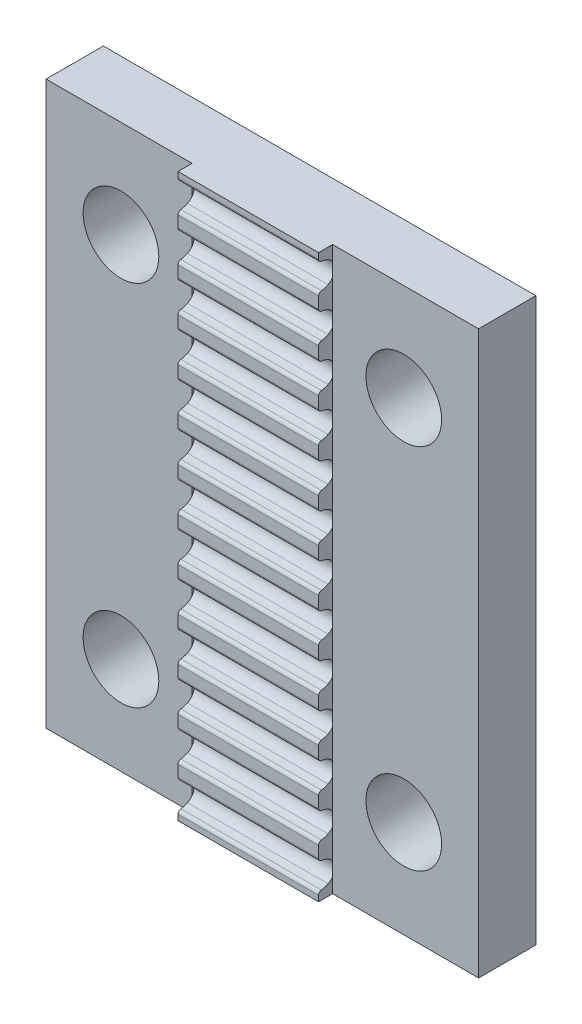
SolidWorks part; units mm, degrees
ref_plane "Piano frontale" through (0, 0, 0) normal (0, 0, 1) x (1, 0, 0)
ref_plane "Piano superiore" through (0, 0, 0) normal (0, 1, 0) x (1, 0, 0)
ref_plane "Piano destro" through (0, 0, 0) normal (1, 0, 0) x (0, 0, -1)
sketch "Schizzo1" plane through (0, 0, 0) normal (0, 0, 1) x (1, 0, 0)
  line L1 (-10, -13) -> (10, -13)
  line L2 (-10, -13) -> (-10, 13)
  line L3 (-10, 13) -> (10, 13)
  line L4 (10, -13) -> (10, 13)
  line L5 (-10, -13) -> (10, 13) construction
  line L6 (-10, 13) -> (10, -13) construction
  line L7 (-6.5385, -8.5) -> (6.5385, -8.5) construction
  line L8 (-6.5385, -8.5) -> (-6.5385, 8.5) construction
  line L9 (-6.5385, 8.5) -> (6.5385, 8.5) construction
  line L10 (6.5385, -8.5) -> (6.5385, 8.5) construction
  line L11 (-6.5385, -8.5) -> (6.5385, 8.5) construction
  line L12 (-6.5385, 8.5) -> (6.5385, -8.5) construction
  line L13 (-3.25, 13) -> (3.25, 13)
  line L14 (-3.25, 13) -> (-3.25, -13)
  line L15 (-3.25, -13) -> (3.25, -13)
  line L16 (3.25, 13) -> (3.25, -13)
  line L17 (-3.25, 13) -> (3.25, -13) construction
  line L18 (-3.25, -13) -> (3.25, 13) construction
  circle A0 centre (-6.5385, 8.5) radius 1.75
  circle A1 centre (6.5385, 8.5) radius 1.75
  circle A2 centre (6.5385, -8.5) radius 1.75
  circle A3 centre (-6.5385, -8.5) radius 1.75
  point P0 (0, 0)
  point P6 (0, 0)
  point P15 (0, 0)
  dimension "D3" = 3.5
  dimension "D1" = 20
  dimension "D2" = 26
  dimension "D4" = 4.5
  dimension "D5" = 6.5
extrude "Estrusione-Estrusione1" add sketch "Schizzo1" along normal blind 1 contours L14 L3 L2 L1 A3 A0 | L16 L3 L14 L1 | L3 L16 L1 L4 A2 A1 region at (-6.6357, 0, 0) region at (0, 0, 0) region at (6.6357, 0, 0)
extrude "Estrusione-Estrusione2" add sketch "Schizzo1<3>" along normal blind 1.65 contours L14 L15 L16 L13
sketch "Schizzo1<3>" plane through (0, 0, 0) normal (0, 0, 1) x (1, 0, 0) same geometry as "Schizzo1"
extrude "Estrusione-Estrusione3" add sketch "Schizzo1<5>" against normal blind 1.65 contours L14 L3 L2 L1 A3 A0 | L16 L3 L14 L1 | L3 L16 L1 L4 A2 A1 region at (-6.6357, 0, 0) region at (0, 0, 0) region at (6.6357, 0, 0)
sketch "Schizzo1<5>" plane through (0, 0, 0) normal (0, 0, 1) x (1, 0, 0) same geometry as "Schizzo1"
sketch "Schizzo2" plane through (-3.25, 0, 0) normal (-1, 0, 0) x (0, 0, 1)
  line L0 (1.65, 13) -> (1.65, 12.7402)
  line L2 (1.65, 13) -> (1, 13) construction
  line L3 (1.65, 13) -> (1, 13) construction
  line L4 (1.65, 11) -> (1.65, 10.7402)
  line L5 (2.28, 11) -> (2.28, 9)
  line L6 (1.65, 9) -> (1.65, 9.2598)
  line L7 (1.65, 13) -> (1.65, -13) construction
  line L8 (1.65, 13) -> (1.65, -13) construction
  line L9 (0.9, 12) -> (2.28, 12) construction
  line L10 (2.28, 13) -> (2.28, 11)
  line L11 (1.65, 11) -> (1.65, 11.2598)
  line L12 (1.65, 11) -> (1, 11) construction
  line L13 (0.9, 10) -> (2.28, 10) construction
  line L14 (1.65, 9) -> (1.65, 8.7402)
  line L15 (2.28, 9) -> (2.28, 7)
  line L16 (1.65, 7) -> (1.65, 7.2598)
  line L17 (1.65, 9) -> (1, 9) construction
  line L18 (0.9, 8) -> (2.28, 8) construction
  line L19 (1.65, 7) -> (1.65, 6.7402)
  line L20 (2.28, 7) -> (2.28, 5)
  line L21 (1.65, 5) -> (1.65, 5.2598)
  line L22 (1.65, 7) -> (1, 7) construction
  line L23 (0.9, 6) -> (2.28, 6) construction
  line L24 (1.65, 5) -> (1.65, 4.7402)
  line L25 (2.28, 5) -> (2.28, 3)
  line L26 (1.65, 3) -> (1.65, 3.2598)
  line L27 (1.65, 5) -> (1, 5) construction
  line L28 (0.9, 4) -> (2.28, 4) construction
  line L29 (1.65, 3) -> (1.65, 2.7402)
  line L30 (2.28, 3) -> (2.28, 1)
  line L31 (1.65, 1) -> (1.65, 1.2598)
  line L32 (1.65, 3) -> (1, 3) construction
  line L33 (0.9, 2) -> (2.28, 2) construction
  line L34 (1.65, 1) -> (1.65, 0.7402)
  line L35 (2.28, 1) -> (2.28, -1)
  line L36 (1.65, -1) -> (1.65, -0.7402)
  line L37 (1.65, 1) -> (1, 1) construction
  line L38 (0.9, 0) -> (2.28, 0) construction
  line L39 (1.65, -1) -> (1.65, -1.2598)
  line L40 (2.28, -1) -> (2.28, -3)
  line L41 (1.65, -3) -> (1.65, -2.7402)
  line L42 (1.65, -1) -> (1, -1) construction
  line L43 (0.9, -2) -> (2.28, -2) construction
  line L44 (1.65, -3) -> (1.65, -3.2598)
  line L45 (2.28, -3) -> (2.28, -5)
  line L46 (1.65, -5) -> (1.65, -4.7402)
  line L47 (1.65, -3) -> (1, -3) construction
  line L48 (0.9, -4) -> (2.28, -4) construction
  line L49 (1.65, -5) -> (1.65, -5.2598)
  line L50 (2.28, -5) -> (2.28, -7)
  line L51 (1.65, -7) -> (1.65, -6.7402)
  line L52 (1.65, -5) -> (1, -5) construction
  line L53 (0.9, -6) -> (2.28, -6) construction
  line L54 (1.65, -7) -> (1.65, -7.2598)
  line L55 (2.28, -7) -> (2.28, -9)
  line L56 (1.65, -9) -> (1.65, -8.7402)
  line L57 (1.65, -7) -> (1, -7) construction
  line L58 (0.9, -8) -> (2.28, -8) construction
  line L59 (1.65, -9) -> (1.65, -9.2598)
  line L60 (2.28, -9) -> (2.28, -11)
  line L61 (1.65, -11) -> (1.65, -10.7402)
  line L62 (1.65, -9) -> (1, -9) construction
  line L63 (0.9, -10) -> (2.28, -10) construction
  line L64 (1.65, -11) -> (1.65, -11.2598)
  line L65 (2.28, -11) -> (2.28, -13)
  line L66 (1.65, -13) -> (1.65, -12.7402)
  line L67 (1.65, -11) -> (1, -11) construction
  line L68 (0.9, -12) -> (2.28, -12) construction
  line L69 (1.65, -13) -> (2.28, -13)
  line L70 (2.28, 13) -> (1.65, 13)
  arc A0 (1.65, 12.7402) -> (1.5196, 12.5915) centre (1.5, 12.7402) cw
  arc A1 (1.2118, 12.4989) -> (1.5196, 12.5915) centre (1.65, 11.6) cw
  arc A2 (1.65, 10.7402) -> (1.5196, 10.5915) centre (1.5, 10.7402) cw
  arc A3 (1.2118, 10.4989) -> (1.5196, 10.5915) centre (1.65, 9.6) cw
  arc A4 (1.2118, 10.4989) -> (1.2118, 9.5011) centre (1.455, 10) ccw
  arc A5 (1.2118, 12.4989) -> (1.2118, 11.5011) centre (1.455, 12) ccw
  arc A6 (1.2118, 11.5011) -> (1.5196, 11.4085) centre (1.65, 12.4) ccw
  arc A7 (1.65, 11.2598) -> (1.5196, 11.4085) centre (1.5, 11.2598) ccw
  arc A8 (1.2118, 9.5011) -> (1.5196, 9.4085) centre (1.65, 10.4) ccw
  arc A9 (1.65, 9.2598) -> (1.5196, 9.4085) centre (1.5, 9.2598) ccw
  arc A10 (1.65, 8.7402) -> (1.5196, 8.5915) centre (1.5, 8.7402) cw
  arc A11 (1.2118, 8.4989) -> (1.5196, 8.5915) centre (1.65, 7.6) cw
  arc A12 (1.2118, 8.4989) -> (1.2118, 7.5011) centre (1.455, 8) ccw
  arc A13 (1.2118, 7.5011) -> (1.5196, 7.4085) centre (1.65, 8.4) ccw
  arc A14 (1.65, 7.2598) -> (1.5196, 7.4085) centre (1.5, 7.2598) ccw
  arc A15 (1.65, 6.7402) -> (1.5196, 6.5915) centre (1.5, 6.7402) cw
  arc A16 (1.2118, 6.4989) -> (1.5196, 6.5915) centre (1.65, 5.6) cw
  arc A17 (1.2118, 6.4989) -> (1.2118, 5.5011) centre (1.455, 6) ccw
  arc A18 (1.2118, 5.5011) -> (1.5196, 5.4085) centre (1.65, 6.4) ccw
  arc A19 (1.65, 5.2598) -> (1.5196, 5.4085) centre (1.5, 5.2598) ccw
  arc A20 (1.65, 4.7402) -> (1.5196, 4.5915) centre (1.5, 4.7402) cw
  arc A21 (1.2118, 4.4989) -> (1.5196, 4.5915) centre (1.65, 3.6) cw
  arc A22 (1.2118, 4.4989) -> (1.2118, 3.5011) centre (1.455, 4) ccw
  arc A23 (1.2118, 3.5011) -> (1.5196, 3.4085) centre (1.65, 4.4) ccw
  arc A24 (1.65, 3.2598) -> (1.5196, 3.4085) centre (1.5, 3.2598) ccw
  arc A25 (1.65, 2.7402) -> (1.5196, 2.5915) centre (1.5, 2.7402) cw
  arc A26 (1.2118, 2.4989) -> (1.5196, 2.5915) centre (1.65, 1.6) cw
  arc A27 (1.2118, 2.4989) -> (1.2118, 1.5011) centre (1.455, 2) ccw
  arc A28 (1.2118, 1.5011) -> (1.5196, 1.4085) centre (1.65, 2.4) ccw
  arc A29 (1.65, 1.2598) -> (1.5196, 1.4085) centre (1.5, 1.2598) ccw
  arc A30 (1.65, 0.7402) -> (1.5196, 0.5915) centre (1.5, 0.7402) cw
  arc A31 (1.2118, 0.4989) -> (1.5196, 0.5915) centre (1.65, -0.4) cw
  arc A32 (1.2118, 0.4989) -> (1.2118, -0.4989) centre (1.455, 0) ccw
  arc A33 (1.2118, -0.4989) -> (1.5196, -0.5915) centre (1.65, 0.4) ccw
  arc A34 (1.65, -0.7402) -> (1.5196, -0.5915) centre (1.5, -0.7402) ccw
  arc A35 (1.65, -1.2598) -> (1.5196, -1.4085) centre (1.5, -1.2598) cw
  arc A36 (1.2118, -1.5011) -> (1.5196, -1.4085) centre (1.65, -2.4) cw
  arc A37 (1.2118, -1.5011) -> (1.2118, -2.4989) centre (1.455, -2) ccw
  arc A38 (1.2118, -2.4989) -> (1.5196, -2.5915) centre (1.65, -1.6) ccw
  arc A39 (1.65, -2.7402) -> (1.5196, -2.5915) centre (1.5, -2.7402) ccw
  arc A40 (1.65, -3.2598) -> (1.5196, -3.4085) centre (1.5, -3.2598) cw
  arc A41 (1.2118, -3.5011) -> (1.5196, -3.4085) centre (1.65, -4.4) cw
  arc A42 (1.2118, -3.5011) -> (1.2118, -4.4989) centre (1.455, -4) ccw
  arc A43 (1.2118, -4.4989) -> (1.5196, -4.5915) centre (1.65, -3.6) ccw
  arc A44 (1.65, -4.7402) -> (1.5196, -4.5915) centre (1.5, -4.7402) ccw
  arc A45 (1.65, -5.2598) -> (1.5196, -5.4085) centre (1.5, -5.2598) cw
  arc A46 (1.2118, -5.5011) -> (1.5196, -5.4085) centre (1.65, -6.4) cw
  arc A47 (1.2118, -5.5011) -> (1.2118, -6.4989) centre (1.455, -6) ccw
  arc A48 (1.2118, -6.4989) -> (1.5196, -6.5915) centre (1.65, -5.6) ccw
  arc A49 (1.65, -6.7402) -> (1.5196, -6.5915) centre (1.5, -6.7402) ccw
  arc A50 (1.65, -7.2598) -> (1.5196, -7.4085) centre (1.5, -7.2598) cw
  arc A51 (1.2118, -7.5011) -> (1.5196, -7.4085) centre (1.65, -8.4) cw
  arc A52 (1.2118, -7.5011) -> (1.2118, -8.4989) centre (1.455, -8) ccw
  arc A53 (1.2118, -8.4989) -> (1.5196, -8.5915) centre (1.65, -7.6) ccw
  arc A54 (1.65, -8.7402) -> (1.5196, -8.5915) centre (1.5, -8.7402) ccw
  arc A55 (1.65, -9.2598) -> (1.5196, -9.4085) centre (1.5, -9.2598) cw
  arc A56 (1.2118, -9.5011) -> (1.5196, -9.4085) centre (1.65, -10.4) cw
  arc A57 (1.2118, -9.5011) -> (1.2118, -10.4989) centre (1.455, -10) ccw
  arc A58 (1.2118, -10.4989) -> (1.5196, -10.5915) centre (1.65, -9.6) ccw
  arc A59 (1.65, -10.7402) -> (1.5196, -10.5915) centre (1.5, -10.7402) ccw
  arc A60 (1.65, -11.2598) -> (1.5196, -11.4085) centre (1.5, -11.2598) cw
  arc A61 (1.2118, -11.5011) -> (1.5196, -11.4085) centre (1.65, -12.4) cw
  arc A62 (1.2118, -11.5011) -> (1.2118, -12.4989) centre (1.455, -12) ccw
  arc A63 (1.2118, -12.4989) -> (1.5196, -12.5915) centre (1.65, -11.6) ccw
  arc A64 (1.65, -12.7402) -> (1.5196, -12.5915) centre (1.5, -12.7402) ccw
  point P26 (1.65, 12.4)
  point P37 (1.65, 10.4)
  point P57 (1.65, 8.4)
  point P77 (1.65, 6.4)
  point P97 (1.65, 4.4)
  point P117 (1.65, 2.4)
  point P137 (1.65, 0.4)
  point P157 (1.65, -1.6)
  point P177 (1.65, -3.6)
  point P197 (1.65, -5.6)
  point P217 (1.65, -7.6)
  point P237 (1.65, -9.6)
  point P257 (1.65, -11.6)
  dimension "D2" = 1
  dimension "D3" = 0.15
  dimension "D4" = 0.75
  dimension "D5" = 1.38
  dimension "D6" = 1
  dimension "D7" = 13
  dimension "D8" = 0.63
  dimension "D9" = 0.4
extrude "Taglio-Estrusione1" cut sketch "Schizzo2" against normal up to surface (6.5 mm away) up to face at (3.25, 0, 1.325)
